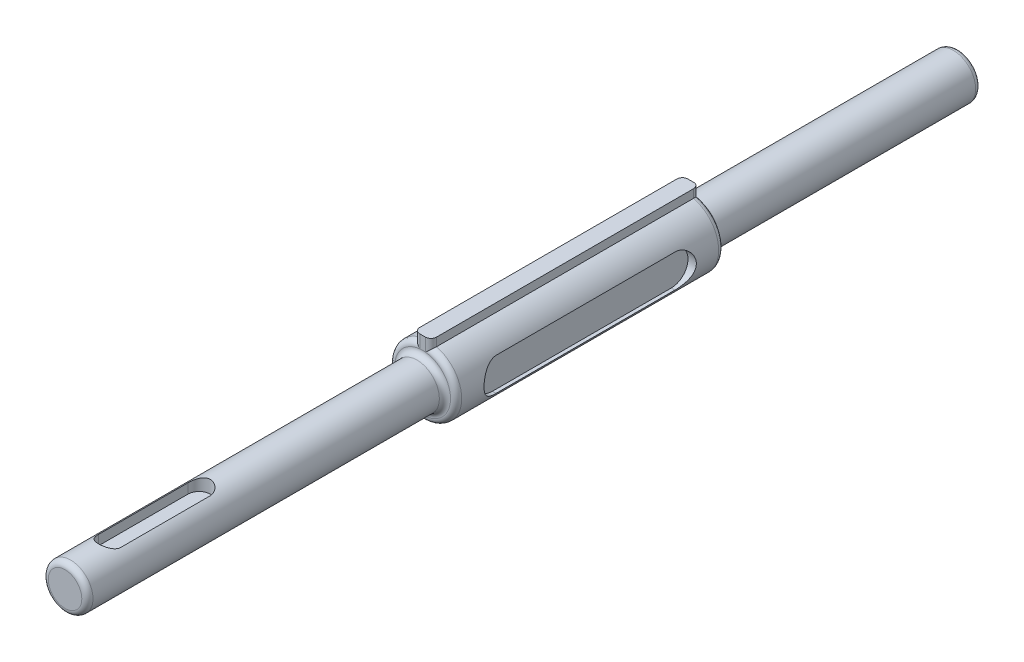
SolidWorks part; units mm, degrees
material "AISI 1020"
ref_plane "Front Plane" through (0, 0, 0) normal (0, 0, 1) x (1, 0, 0)
ref_plane "Top Plane" through (0, 0, 0) normal (0, 1, 0) x (1, 0, 0)
ref_plane "Right Plane" through (0, 0, 0) normal (1, 0, 0) x (0, 0, -1)
sketch "Sketch1" plane through (0, 0, 0) normal (0, 0, 1) x (1, 0, 0)
  line L0 (1.1906, 4.6113) -> (1.1906, 5.8019)
  line L1 (1.1906, 5.8019) -> (-1.1906, 5.8019)
  line L2 (-1.1906, 5.8019) -> (-1.1906, 4.6113)
  arc A0 (-1.1906, 4.6113) -> (1.1906, 4.6113) centre (0, 0) ccw
  point P4 (0, 5.8019)
  dimension "D1" = 4.7625
  dimension "D2" = 1.1906
  dimension "D3" = 2.3813
extrude "Boss-Extrude1" add sketch "Sketch1" along normal blind 38.1
sketch "Sketch2" plane through (0, 0, 0) normal (0, 0, -1) x (-1, 0, 0)
  circle A0 centre (0, 0) radius 3.175
  dimension "D1" = 6.35
extrude "Boss-Extrude2" add sketch "Sketch2" along normal blind 38.1
sketch "Sketch3" plane through (0, 0, 38.1) normal (0, 0, 1) x (1, 0, 0)
  circle A0 centre (0, 0) radius 3.175
  dimension "D1" = 6.35
extrude "Boss-Extrude3" add sketch "Sketch3" along normal blind 50.8
fillet "Fillet1" radius 0.7937 10 edges at (0, -4.7625, 0) (-3.175, 0, 0) (3.175, 0, 38.1) (0, -4.7625, 38.1) (1.1906, 5.2066, 0) (-1.1906, 5.2066, 0) (1.1906, 5.2066, 38.1) (-1.1906, 5.2066, 38.1) (-3.175, 0, -38.1) (3.175, 0, 88.9)
ref_plane "Plane1" through (0, 0, 0) normal (1, 0, 0) x (0, 0, -1)
ref_plane "Plane2" through (4.7625, 0, 0) normal (1, 0, 0) x (0, 0, -1)
sketch "Sketch4" plane through (4.7625, 0, 0) normal (1, 0, 0) x (0, 0, -1)
  line L0 (-37.3062, -0.0756) -> (-0.7938, -0.0756) construction
  line L1 (-37.3062, 4.6113) -> (-37.3062, -4.7625) construction
  line L2 (-0.7938, -4.7625) -> (-0.7938, 4.6113) construction
  line L3 (-31.75, -0.0756) -> (-6.35, -0.0756) construction
  line L4 (-31.75, 2.3056) -> (-6.35, 2.3056)
  line L5 (-31.75, -2.4569) -> (-6.35, -2.4569)
  arc A0 (-31.75, 2.3056) -> (-31.75, -2.4569) centre (-31.75, -0.0756) ccw
  arc A1 (-6.35, -2.4569) -> (-6.35, 2.3056) centre (-6.35, -0.0756) ccw
  point P8 (-19.05, -0.0756)
  point P13 (-19.05, -0.0756)
  dimension "D1" = 2.3813
  dimension "D2" = 12.7
extrude "Cut-Extrude1" cut sketch "Sketch4" against normal blind 1.1906
ref_plane "Plane3" through (0, 5.8019, 0) normal (0, 1, 0) x (1, 0, 0)
sketch "Sketch5" plane through (0, 5.8019, 0) normal (0, 1, 0) x (1, 0, 0)
  line L0 (0, -38.8938) -> (0, -88.9) construction
  line L1 (3.175, -38.8938) -> (-3.175, -38.8938) construction
  line L2 (-3.175, -88.9) -> (3.175, -88.9) construction
  line L3 (0, -82.55) -> (0, -69.85) construction
  line L4 (-1.5875, -82.55) -> (-1.5875, -69.85)
  line L5 (1.5875, -82.55) -> (1.5875, -69.85)
  arc A0 (-1.5875, -82.55) -> (1.5875, -82.55) centre (0, -82.55) ccw
  arc A1 (1.5875, -69.85) -> (-1.5875, -69.85) centre (0, -69.85) ccw
  point P8 (0, -76.2)
  dimension "D1" = 1.5875
  dimension "D2" = 12.7
  dimension "D3" = 6.35
extrude "Cut-Extrude2" cut sketch "Sketch5" against normal blind 4.445
